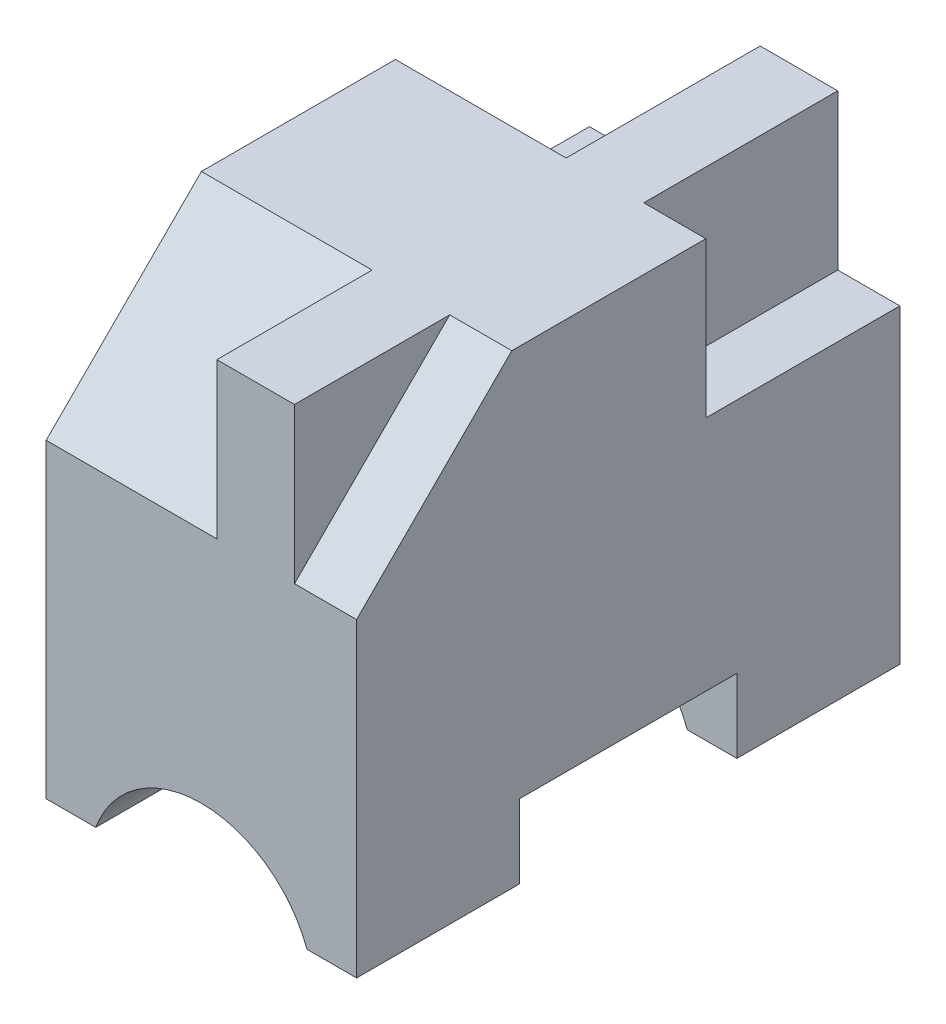
SolidWorks part; units mm, degrees
ref_plane "Спереди" through (0, 0, 0) normal (0, 0, 1) x (1, 0, 0)
ref_plane "Сверху" through (0, 0, 0) normal (0, 1, 0) x (1, 0, 0)
ref_plane "Справа" through (0, 0, 0) normal (1, 0, 0) x (0, 0, -1)
sketch "Эскиз1" plane through (0, 0, 0) normal (0, 0, 1) x (1, 0, 0)
  line L0 (-20, -10) -> (-7, 30)
  line L1 (-20, -30) -> (20, -30)
  line L2 (-20, -30) -> (-20, 30)
  line L3 (-20, 30) -> (20, 30)
  line L4 (20, -30) -> (20, 30)
  line L5 (-20, -30) -> (20, 30) construction
  line L6 (-20, 30) -> (20, -30) construction
  circle A0 centre (0, -35) radius 14.5
  point P0 (0, 0)
  dimension "D5" = 29
  dimension "D1" = 40
  dimension "D2" = 60
  dimension "D3" = 13
  dimension "D4" = 40
  dimension "D6" = 5
extrude "Бобышка-Вытянуть1" add sketch "Эскиз1" along normal blind 70 contours A0 L1 L4 L3 L0 L2 | L3 L2 L0 region at (-15.6667, 16.6667, 0) region at (2.0869, 0.2932, 0)
sketch "Эскиз2" plane through (-20, 0, 0) normal (-1, 0, 0) x (0, 0, 1)
  line L0 (35, -30) -> (35, 30) construction
  line L1 (70, -30) -> (0, -30) construction
  line L3 (70, 30) -> (0, 30) construction
  line L4 (21, -30) -> (49, -30)
  line L5 (21, -30) -> (21, -20.5)
  line L6 (21, -20.5) -> (49, -20.5)
  line L7 (49, -30) -> (49, -20.5)
  line L8 (21, -30) -> (49, -20.5) construction
  line L9 (21, -20.5) -> (49, -30) construction
  point P6 (35, -25.25)
  dimension "D1" = 28
  dimension "D2" = 9.5
extrude "Вырез-Вытянуть1" cut sketch "Эскиз2" against normal through all
sketch "Эскиз3" plane through (20, 0, 0) normal (1, 0, 0) x (0, 0, -1)
  line L0 (-70, 30) -> (-70, 10)
  line L1 (-70, -30) -> (-70, 30) construction
  line L2 (-70, 10) -> (-50, 30)
  line L3 (-70, 30) -> (0, 30) construction
  line L4 (-50, 30) -> (-70, 30)
  line L6 (0, 30) -> (-25, 30)
  line L7 (0, 30) -> (0, 10)
  line L8 (0, 10) -> (-25, 10)
  line L9 (-25, 30) -> (-25, 10)
  dimension "D1" = 20
  dimension "D2" = 25
extrude "Вырез-Вытянуть2" cut sketch "Эскиз3" against normal blind 8
extrude "Вырез-Вытянуть3" cut sketch "Эскиз3<2>" against normal through all from offset 18 offset against normal yes
sketch "Эскиз3<2>" plane through (20, 0, 0) normal (1, 0, 0) x (0, 0, -1) same geometry as "Эскиз3"
